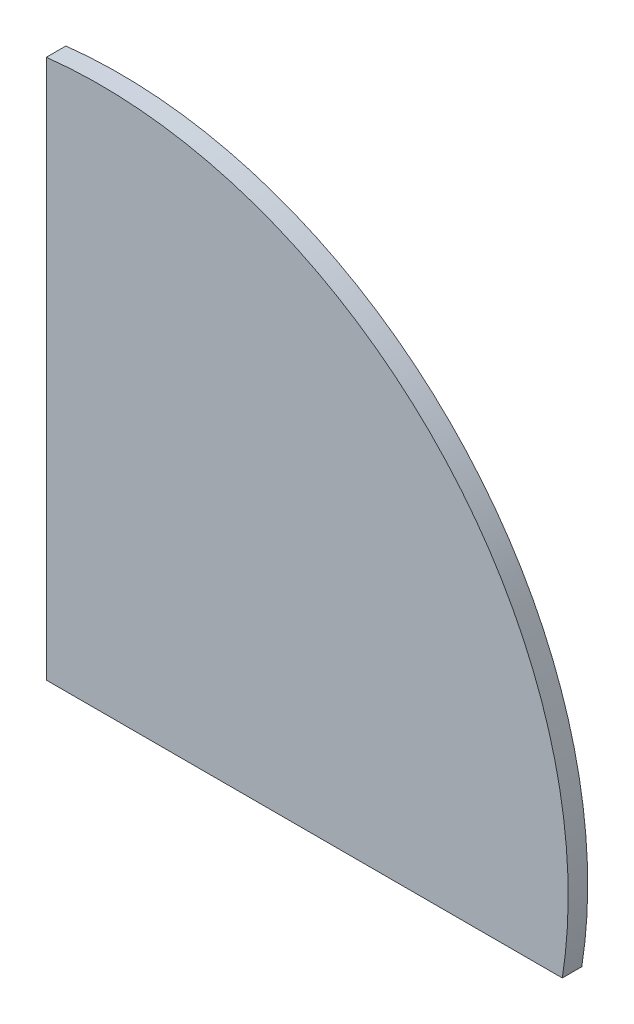
SolidWorks part; units mm, degrees
ref_plane "Front Plane" through (0, 0, 0) normal (0, 0, 1) x (1, 0, 0)
ref_plane "Top Plane" through (0, 0, 0) normal (0, 1, 0) x (1, 0, 0)
ref_plane "Right Plane" through (0, 0, 0) normal (1, 0, 0) x (0, 0, -1)
ref_plane "Plane1" through (0, 0, 65) normal (0, 0, 1) x (1, 0, 0)
sketch "Sketch1" plane through (0, 0, 65) normal (0, 0, 1) x (1, 0, 0)
  circle A0 centre (0, 0) radius 240
extrude "Boss-Extrude1" add sketch "Sketch1" along normal blind 10
sketch "Sketch2" plane through (0, 0, 65) normal (0, 0, -1) x (-1, 0, 0)
  circle A1 centre (0, 0) radius 240 construction
  circle A2 centre (0, 0) radius 230
  circle A3 centre (0, 0) radius 230
  circle A4 centre (0, 0) radius 240
  dimension "D1" = 10
extrude "Boss-Extrude2" add sketch "Sketch2" along normal up to surface (102.52 mm away)
sketch "Sketch3" plane through (0, 0, -37.52) normal (0, 0, -1) x (-1, 0, 0)
  line L0 (27.411, 179.1677) -> (27.411, 135.5)
  line L1 (27.411, 178.739) -> (27.411, 238.4295)
  line L2 (27.411, 135.5) -> (27.411, -223.5261)
  line L3 (-87.3847, -223.5261) -> (27.411, -223.5261)
  arc A0 (20.0515, 167.4551) -> (26.1236, 184.8082) centre (14.411, 179.1677) ccw construction
  circle A4 centre (0, 0) radius 240
  arc A5 (27.411, 238.4295) -> (-87.3847, -223.5261) centre (0, 0) ccw
  circle M2 centre (0, 0) radius 230
  circle M3 centre (0, 0) radius 240
  dimension "D2" = 0
extrude "Cut-Extrude1" cut sketch "Sketch3" against normal through all contours L0 L1 M2 | L1 M2 M3 region at (-111.9186, -1.2669, -37.52) region at (-33.2082, 233.3951, -37.52)
sketch "Sketch4" plane through (0, 0, -37.52) normal (0, 0, -1) x (-1, 0, 0)
  line L0 (38.1, 226.7922) -> (37.0861, 226.7922) construction
  line L1 (-37.0861, 226.7922) -> (-38.1, 226.7922) construction
  line L2 (38.1, 226.7922) -> (37.0861, 226.7922)
  line L3 (-37.0861, 226.7922) -> (-38.1, 226.7922)
  line L4 (-38.1, 226.7922) -> (38.1, 226.7922)
  line L5 (-38.1, 226.7922) -> (-38.1, 236.9565)
  line L6 (38.1, 226.7922) -> (38.1, 238.4295)
  line L7 (38.1, 238.4295) -> (27.411, 238.4295)
  arc A0 (27.411, 238.4295) -> (-87.3847, -223.5261) centre (0, 0) ccw construction
  arc A1 (27.411, 238.4295) -> (-38.1, 236.9565) centre (0, 0) ccw
sketch "Sketch5" plane through (0, 0, -37.52) normal (0, 0, -1) x (-1, 0, 0)
  line L1 (27.411, 228.3608) -> (27.411, 238.4295)
  line L2 (-238.9392, -38.2078) -> (-75.4978, -38.2078) construction
  line L3 (-236.9392, -38.2078) -> (-226.8042, -38.2078)
  arc A0 (27.411, 228.3608) -> (-54.1856, -223.5261) centre (0, 0) ccw construction
  arc A1 (27.411, 238.4295) -> (-87.3847, -223.5261) centre (0, 0) ccw construction
  arc A2 (27.411, 228.3608) -> (-226.8042, -38.2078) centre (0, 0) ccw
  arc A3 (27.411, 238.4295) -> (-236.9392, -38.2078) centre (0, 0) ccw
extrude "Boss-Extrude4" add sketch "Sketch5" along normal up to surface (6 mm away)
sketch "Sketch7" plane through (0, 0, 0) normal (1, 0, 0) x (0, 0, -1)
  line L3 (-26.398, -50.2078) -> (37.52, -50.2078)
  line L4 (-27.418, -49.1878) -> (-27.418, -37.9678)
  line L5 (-27.418, -37.9678) -> (43.52, -37.9678)
  line L6 (43.52, -37.9678) -> (43.52, -50.2078)
  line L7 (43.52, -50.2078) -> (37.52, -50.2078)
  line L8 (-26.398, -50.2078) -> (-27.418, -50.2078)
  line L9 (-27.418, -50.2078) -> (-27.418, -49.1878)
extrude "Cut-Extrude2" cut sketch "Sketch7" along normal through all
sketch "Sketch9" plane through (0, 0, -43.52) normal (0, 0, -1) x (-1, 0, 0)
  line L0 (-226.8445, -37.9678) -> (-236.9777, -37.9678) construction
  line L1 (-226.8445, -37.9678) -> (-236.9777, -37.9678)
  line L2 (27.411, 238.4295) -> (27.411, -37.9678)
  line L3 (27.411, -37.9678) -> (-226.8445, -37.9678)
  arc A0 (27.411, 238.4295) -> (-236.9777, -37.9678) centre (0, 0) ccw construction
  arc A1 (27.411, 238.4295) -> (-236.9777, -37.9678) centre (0, 0) ccw
extrude "Boss-Extrude6" add sketch "Sketch9" along normal blind 10
sketch "Sketch10" plane through (0, 0, 75) normal (0, 0, 1) x (1, 0, 0)
  line L2 (-27.411, 238.4295) -> (-27.411, -223.5261)
  line L3 (-27.411, -223.5261) -> (87.3847, -223.5261)
  line L4 (-27.411, 238.4295) -> (-27.411, -223.5261)
  line L5 (-27.411, -223.5261) -> (87.3847, -223.5261)
  arc A1 (87.3847, -223.5261) -> (-27.411, 238.4295) centre (0, 0) ccw
  arc A2 (87.3847, -223.5261) -> (-27.411, 238.4295) centre (0, 0) ccw
  dimension "D1" = 0
extrude "Cut-Extrude3" cut sketch "Sketch10" against normal up to surface (118.52 mm away) up to face at (79.5557, 72.0163, -43.52)
